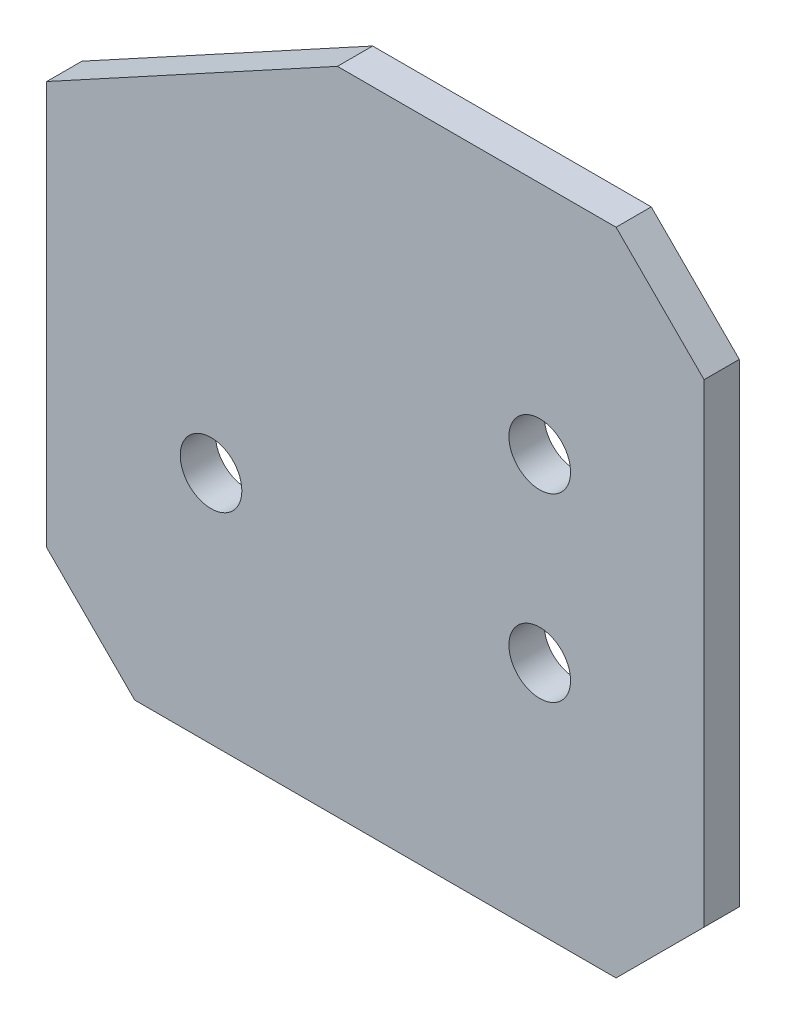
SolidWorks part; units mm, degrees
note: The reader was unsure of these and kept them because the rebuilt part matched: thickness of "Базовая кромка1", "Листовой металл3", "Листовой металл4".
material "AISI 1020"
ref_plane "Спереди" through (0, 0, 0) normal (0, 0, 1) x (1, 0, 0)
ref_plane "Сверху" through (0, 0, 0) normal (0, 1, 0) x (1, 0, 0)
ref_plane "Справа" through (0, 0, 0) normal (1, 0, 0) x (0, 0, -1)
sketch "Эскиз1" plane through (0, 0, 0) normal (0, 0, 1) x (1, 0, 0)
  line L0 (0, -1000) -> (0, 49000) construction
  line L1 (56, 3) -> (-56, 3)
  line L2 (-530.3264, 86.7738) -> (144.1634, 86.7738) construction
  line L3 (-56, 3) -> (-56, 113.7738)
  line L5 (-537.2086, 113.7738) -> (144.1634, 113.7738) construction
  line L6 (-56, 113.7738) -> (56, 113.7738)
  line L7 (133.9446, 3) -> (-133.9446, 3) construction
  line L8 (133.9446, 3) -> (-133.9446, 3) construction
  line L9 (-15, 30) -> (-15, 86.7738) construction
  line L10 (164.1634, 30) -> (-740.8168, 30) construction
  line L11 (0, 73.7738) -> (-56, 73.7738) construction
  line L12 (56, 3) -> (56, 113.7738)
  circle A0 centre (-28, 73.7738) radius 5.25 construction
  circle A1 centre (-28, 73.7738) radius 13 construction
  circle A2 centre (-28, 43) radius 5.25
  circle A3 centre (-28, 43) radius 13 construction
  circle A4 centre (28, 73.7738) radius 5.25
  circle A5 centre (28, 43) radius 5.25
  point P27 (-28, 73.7738)
  point P33 (0, 3)
  point P34 (0, 113.7738)
  dimension "D1" = 10.5
  dimension "D2" = 26
base flange "Базовая кромка1" sketch "Эскиз1" thickness 6 reverse thickness direction no parameters "D1"=0.74
chamfer "Фаска1" distance 15 angle 45 4 edges at (56, 3, -3) (-56, 3, -3) (56, 113.7738, -3) (-56, 113.7738, -3)
sketch "Эскиз2" plane through (0, 0, 0) normal (0, 0, 1) x (1, 0, 0)
  line L0 (-56, 113.7738) -> (-56, 86.7684)
  line L1 (-56, 3) -> (-56, 113.7738) construction
  line L2 (-56, 86.7684) -> (-6.4685, 113.7738)
  line L3 (-56, 113.7738) -> (56, 113.7738) construction
  line L4 (-6.4685, 113.7738) -> (-56, 113.7738)
  line L5 (-6.4685, 113.7738) -> (-160.121, 30) construction
extrude "Вырез-Вытянуть1" cut sketch "Эскиз2" against normal blind 10
sketch "Сгиб-Линии1" [suppressed] plane through (0, 0, 0) normal (0, 1, 0) x (1, 0, 0)
sketch "Граничная рамка1" [suppressed] plane through (0, 0, 0) normal (0, 1, 0) x (1, 0, 0)
sheet metal parameters "Листовой металл3" thickness 6 parameters "D1"=0.74, "D7"=4
flat pattern "Развертка3" [suppressed]
sketch "Сгиб-Линии2" plane through (0, 0, 0) normal (0, 1, 0) x (1, 0, 0)
sketch "Граничная рамка2" [suppressed] plane through (0, 0, 0) normal (0, 1, 0) x (1, 0, 0)
sheet metal parameters "Листовой металл4" thickness 6 parameters "D1"=0.74, "D7"=4
flat pattern "Развертка3"
sketch "Сгиб-Линии2" plane through (0, 0, 0) normal (0, 1, 0) x (1, 0, 0)
sketch3d "Граничная рамка2" [suppressed]
  line L0 (-56, 3, 0) -> (56, 3, 0) construction
  line L1 (-56, 113.7738, 0) -> (56, 113.7738, 0) construction
  line L2 (-56, 3, 0) -> (-56, 113.7738, 0) construction
  line L3 (56, 3, 0) -> (56, 113.7738, 0) construction
